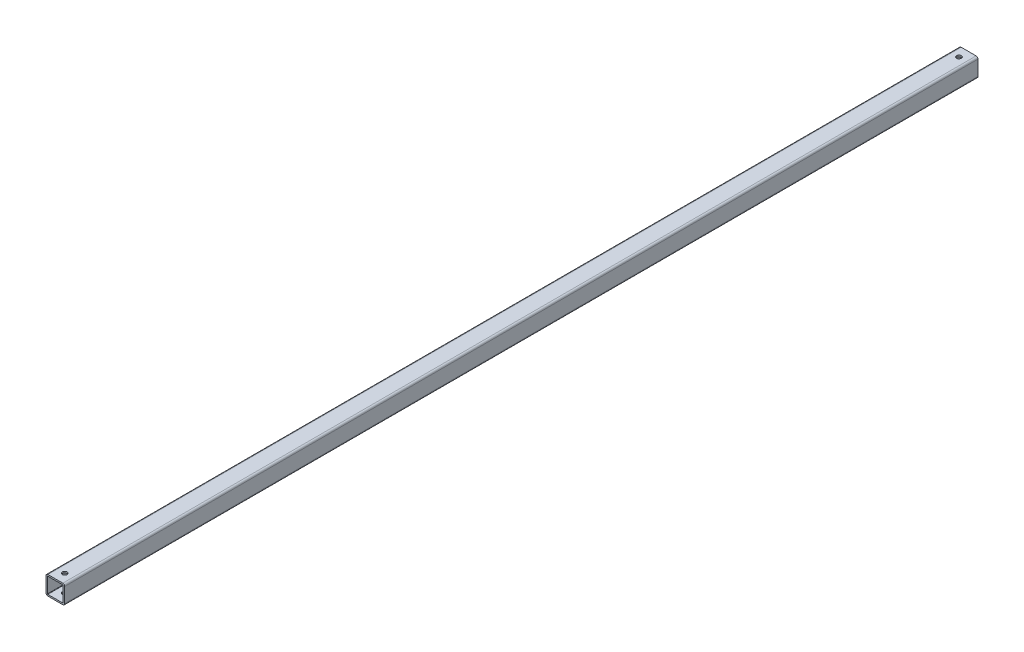
SolidWorks part; units mm, degrees
material "6063-T4"
ref_plane "Front Plane" through (0, 0, 0) normal (0, 0, 1) x (1, 0, 0)
ref_plane "Top Plane" through (0, 0, 0) normal (0, 1, 0) x (1, 0, 0)
ref_plane "Right Plane" through (0, 0, 0) normal (1, 0, 0) x (0, 0, -1)
sketch "Sketch1" plane through (0, 0, 0) normal (0, 0, 1) x (1, 0, 0)
  line L1 (10, -12.5) -> (-10, -12.5)
  line L2 (12.5, -10) -> (12.5, 10)
  line L3 (10, 12.5) -> (-10, 12.5)
  line L4 (-12.5, -10) -> (-12.5, 10)
  line L5 (12.5, -12.5) -> (-12.5, 12.5) construction
  line L6 (12.5, 12.5) -> (-12.5, -12.5) construction
  arc A0 (-10, 12.5) -> (-12.5, 10) centre (-10, 10) ccw
  arc A1 (12.5, 10) -> (10, 12.5) centre (10, 10) ccw
  arc A2 (10, -12.5) -> (12.5, -10) centre (10, -10) ccw
  arc A3 (-10, -12.5) -> (-12.5, -10) centre (-10, -10) cw
  point P0 (0, 0)
  dimension "D2" = 2.5
  dimension "D1" = 25
extrude "Extrude-Thin1" add sketch "Sketch1" along normal mid plane 1219.2 thin thin type one direction reverse wall 2
hole_wizard "1/4 (0.25) Diameter Hole1" positions "Sketch2" profile "Sketch3" hole size "1/4" standard "ANSI Inch"
sketch "Sketch2" plane through (0, 12.5, 0) normal (0, 1, 0) x (1, 0, 0)
  line L0 (12.5, -609.6) -> (12.5, 609.6) construction
  line L1 (10, 609.6) -> (-10, 609.6) construction
  line L2 (10, -609.6) -> (-10, -609.6) construction
  point P0 (-0.2, 596.9)
  point P7 (-0.2, -596.9)
  dimension "D1" = 12.7
  dimension "D2" = 12.7
  dimension "D3" = 12.7
  dimension "D4" = 12.7
sketch "Sketch3" plane through (-0.2, 12.5, -596.9) normal (1, 0, 0) x (0, 0, 1)
  line L0 (0, 0) -> (0, 27.3077)
  line L1 (0, 27.3077) -> (3.175, 25.4)
  line L2 (3.175, 25.4) -> (3.175, 0)
  line L5 (3.175, 0) -> (0, 0)
  line L10 (0, 27.3077) -> (-3.175, 25.4) construction
  line L11 (0, -6.35) -> (0, 107.95) construction
  dimension "Hole Dia." = 6.35
  dimension "Hole Depth" = 25.4
  dimension "Drill Angle" = 118
equation "\"D2@Sketch1\" = \"D5@Extrude-Thin1\" * 1.25"
